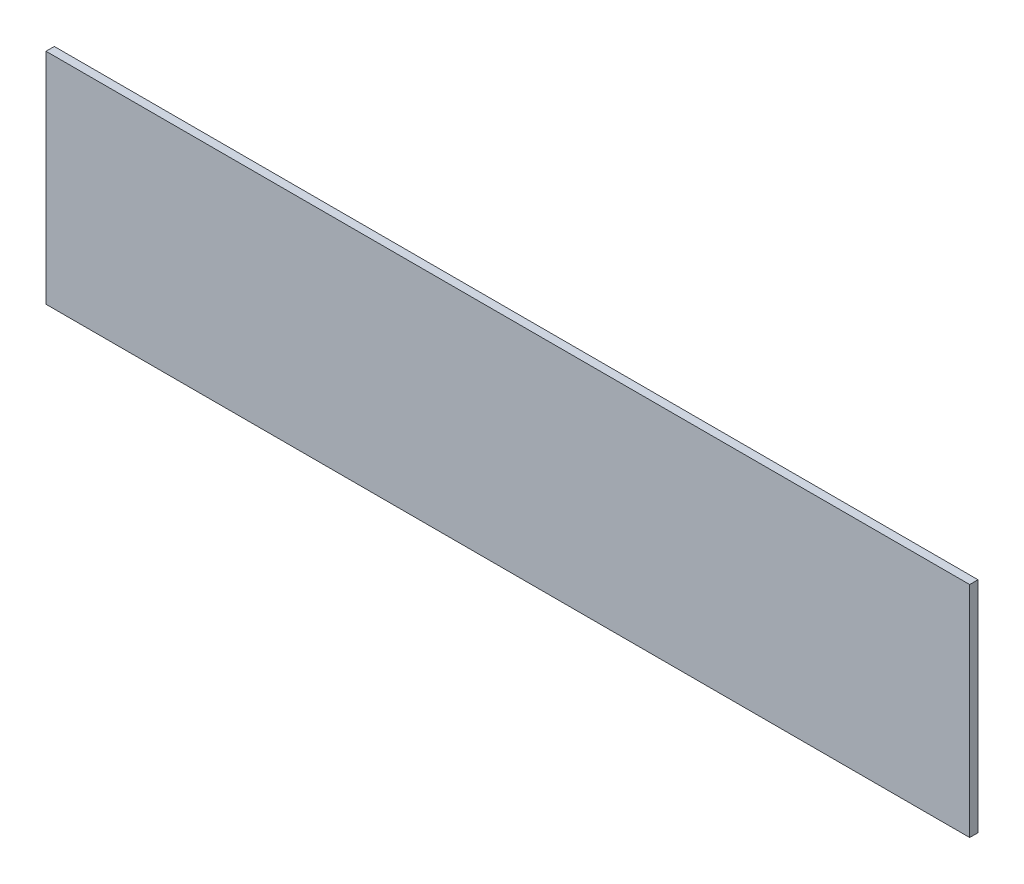
SolidWorks part; units mm, degrees
material "ABS"
ref_plane "X-Y Datum" through (0, 0, 0) normal (0, 0, 1) x (1, 0, 0)
ref_plane "X-Z Datum" through (0, 0, 0) normal (0, 1, 0) x (1, 0, 0)
ref_plane "Y-Z Datum" through (0, 0, 0) normal (1, 0, 0) x (0, 0, -1)
sketch "Sketch1" plane through (0, 0, 0) normal (0, 0, 1) x (1, 0, 0)
  line L1 (-176.2, 41.8) -> (176.2, 41.8)
  line L2 (-176.2, 41.8) -> (-176.2, -41.8)
  line L3 (-176.2, -41.8) -> (176.2, -41.8)
  line L4 (176.2, 41.8) -> (176.2, -41.8)
  line L5 (-176.2, 41.8) -> (176.2, -41.8) construction
  line L6 (-176.2, -41.8) -> (176.2, 41.8) construction
  point P0 (0, 0)
  dimension "D1" = 352.4
  dimension "D2" = 83.6
extrude "Boss-Extrude1" add sketch "Sketch1" along normal blind 3.175
